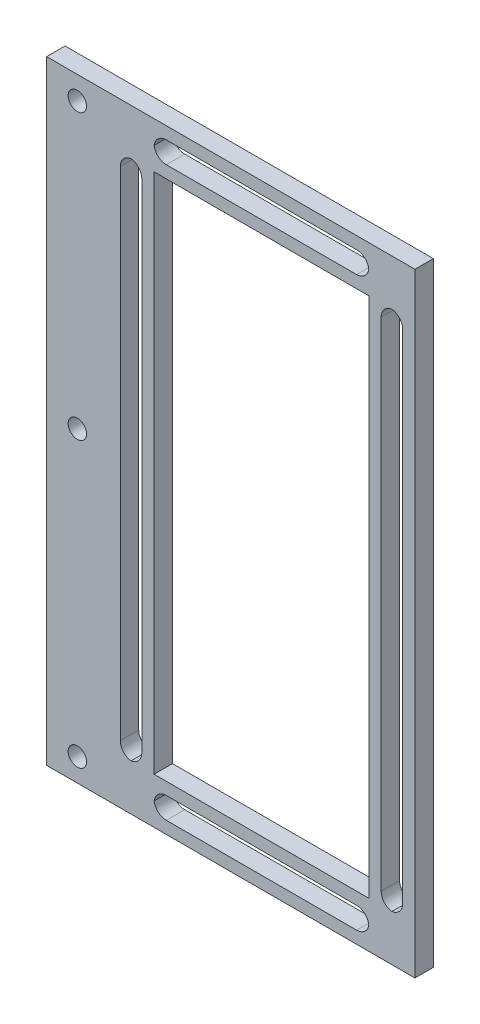
SolidWorks part; units mm, degrees
ref_plane "Front Plane" through (0, 0, 0) normal (0, 0, 1) x (1, 0, 0)
ref_plane "Top Plane" through (0, 0, 0) normal (0, 1, 0) x (1, 0, 0)
ref_plane "Right Plane" through (0, 0, 0) normal (1, 0, 0) x (0, 0, -1)
sketch "Sketch2" plane through (0, 0, 0) normal (0, 0, 1) x (1, 0, 0)
  line L0 (-29.3694, 21.2882) -> (-19.3694, 21.2882) construction
  line L1 (-29.3694, 21.2882) -> (30.6306, 21.2882)
  line L2 (-29.3694, 21.2882) -> (-29.3694, -78.7118)
  line L3 (-29.3694, -78.7118) -> (30.6306, -78.7118)
  line L4 (30.6306, 21.2882) -> (30.6306, -78.7118)
  line L5 (-29.3694, 21.2882) -> (-19.3694, 21.2882)
  line L6 (-29.3694, 21.2882) -> (-29.3694, -78.7118)
  line L7 (-29.3694, -78.7118) -> (-19.3694, -78.7118)
  line L8 (-19.3694, 21.2882) -> (-19.3694, -78.7118)
  line L9 (-19.3694, -78.7118) -> (-11.8694, -78.7118)
  line L10 (-19.3694, -78.7118) -> (-19.3694, -71.2118)
  line L11 (-19.3694, -71.2118) -> (-11.8694, -71.2118)
  line L12 (-11.8694, -78.7118) -> (-11.8694, -71.2118)
  line L13 (30.6306, -78.7118) -> (23.1306, -78.7118)
  line L14 (30.6306, -78.7118) -> (30.6306, -71.2118)
  line L15 (30.6306, -71.2118) -> (23.1306, -71.2118)
  line L16 (23.1306, -78.7118) -> (23.1306, -71.2118)
  line L17 (30.6306, 21.2882) -> (23.1306, 21.2882)
  line L18 (30.6306, 21.2882) -> (30.6306, 13.7882)
  line L19 (30.6306, 13.7882) -> (23.1306, 13.7882)
  line L20 (23.1306, 21.2882) -> (23.1306, 13.7882)
  line L21 (-19.3694, 21.2882) -> (-11.8694, 21.2882)
  line L22 (-19.3694, 21.2882) -> (-19.3694, 13.7882)
  line L23 (-19.3694, 13.7882) -> (-11.8694, 13.7882)
  line L24 (-11.8694, 21.2882) -> (-11.8694, 13.7882)
  line L25 (-11.8694, 13.7882) -> (23.1306, 13.7882)
  line L26 (-11.8694, 13.7882) -> (-11.8694, -71.2118)
  line L27 (-11.8694, -71.2118) -> (23.1306, -71.2118)
  line L28 (23.1306, 13.7882) -> (23.1306, -71.2118)
  line L29 (-17.3694, 19.2882) -> (28.6306, 19.2882)
  line L30 (-17.3694, 19.2882) -> (-17.3694, -76.7118)
  line L31 (-17.3694, -76.7118) -> (28.6306, -76.7118)
  line L32 (28.6306, 19.2882) -> (28.6306, -76.7118)
  line L33 (-13.8694, 15.7882) -> (25.1306, 15.7882)
  line L34 (-13.8694, 15.7882) -> (-13.8694, -73.2118)
  line L35 (-13.8694, -73.2118) -> (25.1306, -73.2118)
  line L36 (25.1306, 15.7882) -> (25.1306, -73.2118)
  line L37 (-24.3694, 21.2882) -> (-24.3694, -78.7118) construction
  line L38 (-13.8694, 15.7882) -> (-13.8694, 19.2882) construction
  line L39 (-19.3694, 17.5382) -> (-29.3694, 17.5382) construction
  circle A0 centre (-24.3694, 17.5382) radius 1.5
  circle A1 centre (-24.3694, -74.9618) radius 1.5
  circle A2 centre (-24.3694, -28.7118) radius 1.5
  dimension "D16" = 3
  dimension "D17" = 3.75
  dimension "D18" = 3
  dimension "D19" = 3
  dimension "D1" = 10
  dimension "D2" = 2
  dimension "D3" = 60
  dimension "D4" = 2
  dimension "D5" = 3.5
  dimension "D6" = 7.5
  dimension "D7" = 7.5
  dimension "D8" = 7.5
  dimension "D9" = 7.5
  dimension "D10" = 3.5
  dimension "D11" = 2
  dimension "D12" = 2
  dimension "D13" = 3.5
  dimension "D14" = 3.5
  dimension "D15" = 100
extrude "Boss-Extrude1" add sketch "Sketch2" along normal blind 3 contours L8 L1 L2 L3 A1 A0 | L30 L23 L8 L11 | L23 L34 L11 L26 | L36 L19 L28 L15 | L19 L32 L15 L4 | L33 L24 L25 L20 | L24 L29 L20 L1 | L34 L33 L24 L29 L30 L23 | L30 L29 L24 L1 L8 L23 | L33 L34 L23 L24 | L36 L33 L20 L19 | L33 L36 L19 L32 L29 L20 | L29 L32 L19 L4 L1 L20 | L34 L35 L12 L11 | L35 L34 L11 L30 L31 L12 | L31 L30 L11 L8 L3 L12 | L31 L12 L3 L16 | L12 L35 L16 L27 | L36 L15 L16 L35 | L15 L36 L35 L16 L31 L32 | L15 L32 L31 L16 L3 L4 region at (-24.3694, 20.2832, 0) region at (-15.6194, 21.1821, 0) region at (5.6306, 20.2882, 0) region at (-18.3694, -28.7118, 0) region at (-19.2633, -74.9618, 0) region at (26.8806, 21.1821, 0) region at (-14.886, 16.8049, 0) region at (5.6306, -77.7118, 0) region at (26.1473, 16.8049, 0) region at (5.6306, 14.7882, 0) region at (-12.8694, 14.7882, 0) region at (-14.886, -74.2285, 0) region at (-12.8694, -28.7118, 0) region at (23.2367, -77.7118, 0) region at (29.6306, -28.7118, 0) region at (24.1306, 14.7882, 0) region at (-12.8694, -72.2118, 0) region at (26.1473, -74.2285, 0) region at (5.6306, -72.2118, 0) region at (24.1306, -28.7118, 0) region at (24.1306, -72.2118, 0)
fillet "Fillet1" radius 2 16 edges at (-11.8694, 15.7882, 1.5) (23.1306, 19.2882, 1.5) (-11.8694, 19.2882, 1.5) (-17.3694, 13.7882, 1.5) (25.1306, 13.7882, 1.5) (28.6306, 13.7882, 1.5) (-13.8694, 13.7882, 1.5) (23.1306, 15.7882, 1.5) (28.6306, -71.2118, 1.5) (-13.8694, -71.2118, 1.5) (25.1306, -71.2118, 1.5) (-17.3694, -71.2118, 1.5) (-11.8694, -76.7118, 1.5) (-11.8694, -73.2118, 1.5) (23.1306, -73.2118, 1.5) (23.1306, -76.7118, 1.5)
